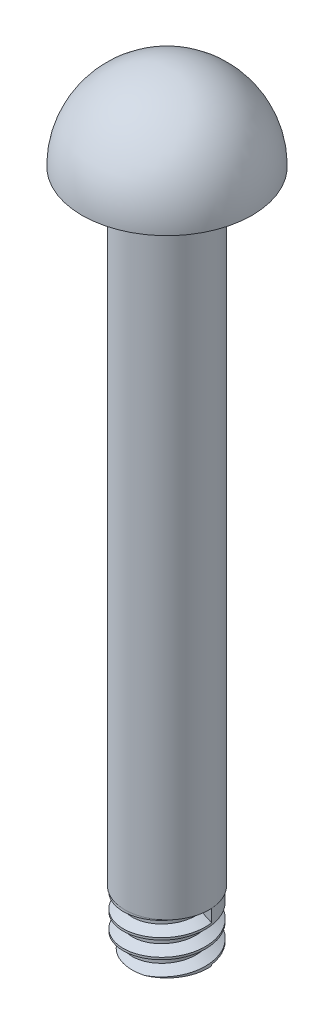
SolidWorks part; units mm, degrees
ref_plane "Front Plane" through (0, 0, 0) normal (0, 0, 1) x (1, 0, 0)
ref_plane "Top Plane" through (0, 0, 0) normal (0, 1, 0) x (1, 0, 0)
ref_plane "Right Plane" through (0, 0, 0) normal (1, 0, 0) x (0, 0, -1)
sketch "Sketch2" plane through (0, 0, 0) normal (0, 1, 0) x (1, 0, 0)
  circle A0 centre (0, 0) radius 12.4
extrude "Boss-Extrude1" add sketch "Sketch2" along normal blind 183
sketch "Sketch3" plane through (0, 183, 0) normal (0, 1, 0) x (1, 0, 0)
  circle A0 centre (0, 0) radius 25
extrude "Boss-Extrude2" add sketch "Sketch3" along normal blind 25 contours A0
fillet "Fillet1" radius 25 1 edges at (0, 208, 25)
sketch "Sketch4" plane through (0, 0, 0) normal (0, -1, 0) x (1, 0, 0)
  circle A0 centre (0, 0) radius 12.1
extrude "Boss-Extrude3" add sketch "Sketch4" along normal blind 15 contours A0
thread "Thread2" pitch 5 method cut trim with start face yes profile "Thread Profile3" start angle 5, offset 4, length 15, pitch 5, diameter 24.2
ref_plane "Plane3" through (12.054, -19, -1.0546) normal (0.0872, 0, 0.9962) x (0.9962, 0, -0.0872)
sketch "Thread Profile3" plane through (12.054, -19, -1.0546) normal (0.0872, 0, 0.9962) x (0.9962, 0, -0.0872)
  line L0 (0, 0) -> (0, 5) construction
  line L11 (0, 0) -> (0, 4.375)
  line L12 (0, 4.375) -> (-2.7063, 2.8125)
  line L13 (-2.7063, 2.8125) -> (-2.7063, 1.5625)
  line L15 (-2.7063, 1.5625) -> (0, 0)
  line L17 (-2.7063, 2.1875) -> (0, 2.1875) construction
  point P2 (0, 0)
  dimension "Pitch" = 5
  dimension "Profile_Angle" = 60
  dimension "Profile_Land" = 1.25
  dimension "Profile_Height" = 2.7063
